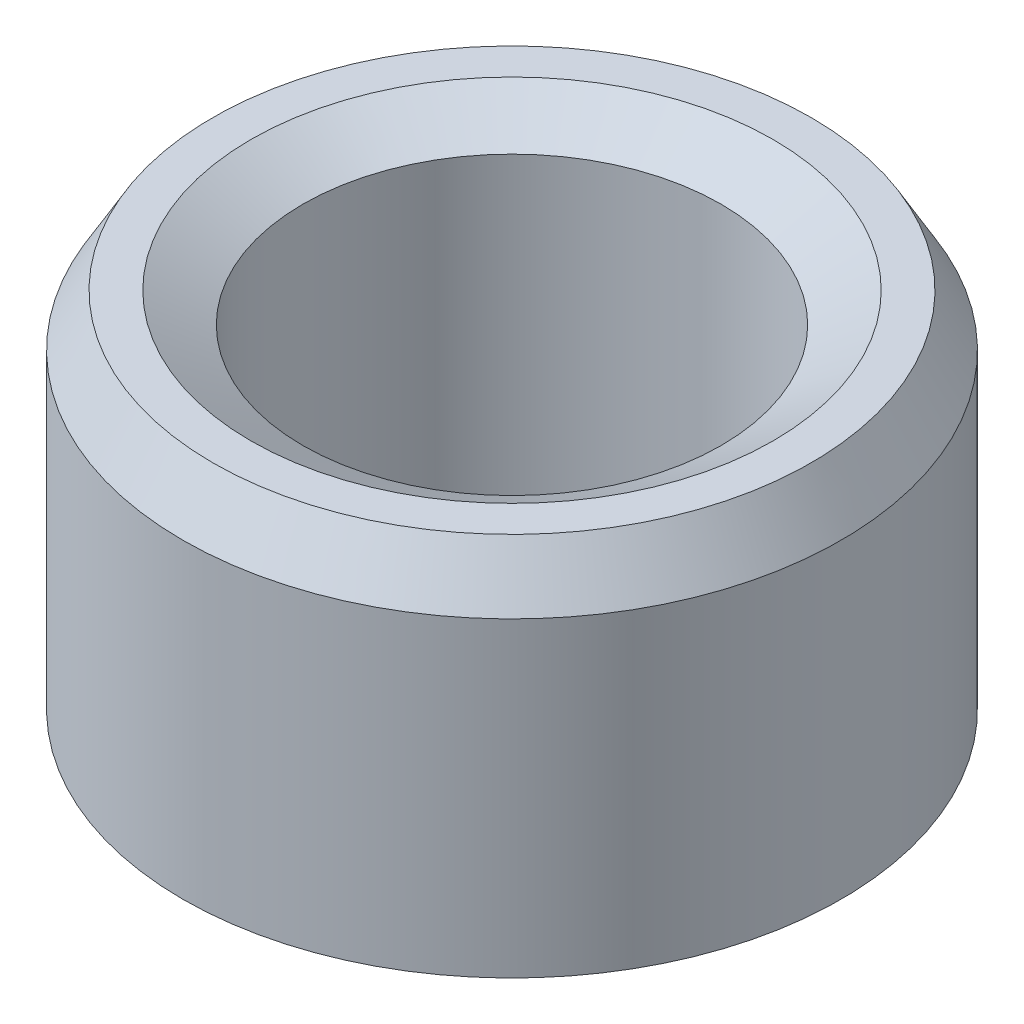
SolidWorks part; units mm, degrees
ref_plane "Front Plane" through (0, 0, 0) normal (0, 0, 1) x (1, 0, 0)
ref_plane "Top Plane" through (0, 0, 0) normal (0, 1, 0) x (1, 0, 0)
ref_plane "Right Plane" through (0, 0, 0) normal (1, 0, 0) x (0, 0, -1)
sketch "Sketch1" plane through (0, 0, 0) normal (0, 1, 0) x (1, 0, 0)
  circle A0 centre (0, 0) radius 17.5
  dimension "SLEEVE_OD" = 35
extrude "Boss-Extrude1" add sketch "Sketch1" along normal blind 20.8947
sketch "Sketch2" plane through (0, 0, 0) normal (0, 1, 0) x (1, 0, 0)
  circle A0 centre (0, 0) radius 11.1178
  dimension "BORE_D" = 22.2355
extrude "Cut-Extrude1" cut sketch "Sketch2" along normal through all
chamfer "Chamfer1" distance 2.7643 angle 30 4 edges at (0, 20.8947, 11.1178) (0, 0, 11.1178) (0, 0, 17.5) (0, 20.8947, 17.5) first distance on face at (0, 20.8947, 11.1178) first distance on face at (0, 0, 11.1178) first distance on face at (0, 20.8947, 17.5)
